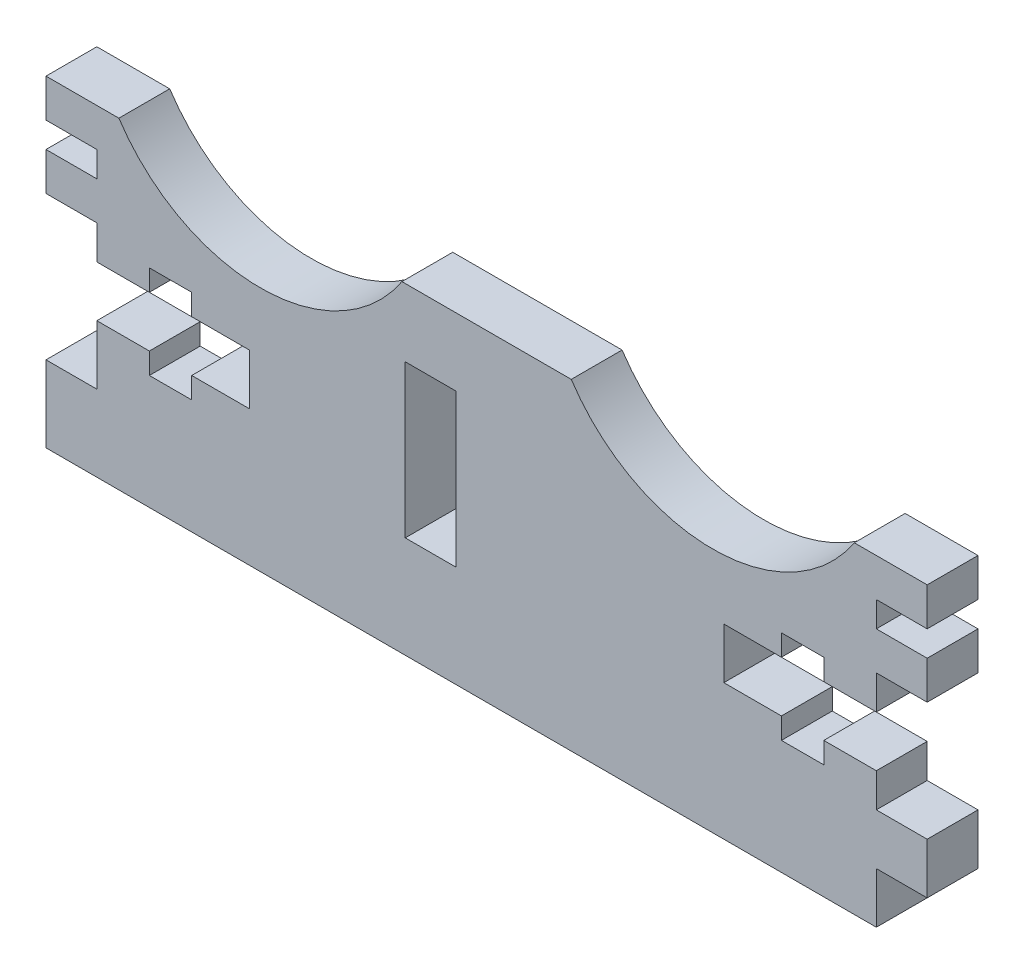
SolidWorks part; units mm, degrees
note: '?' marks a value the reader was unsure of.
material "Acrílico (médio-alto impacto)"
ref_plane "Plano frontal" through (0, 0, 0) normal (0, 0, 1) x (1, 0, 0)
ref_plane "Plano superior" through (0, 0, 0) normal (0, 1, 0) x (1, 0, 0)
ref_plane "Plano direito" through (0, 0, 0) normal (1, 0, 0) x (0, 0, -1)
sketch "Esboço1" plane through (0, 0, 0) normal (0, 0, 1) x (1, 0, 0)
  line L1 (-23, -9.5) -> (23, -9.5)
  line L2 (-23, -9.5) -> (-23, 9.5)
  line L3 (-23, 9.5) -> (23, 9.5)
  line L4 (23, -9.5) -> (23, 9.5)
  line L5 (0, 9.5) -> (0, -9.5) construction
  line L6 (-23, 0) -> (23, 0) construction
  point P0 (0, 0)
  dimension "D1" = 19
  dimension "D2" = 46
sketch "Esboço3" plane through (0, 0, 0) normal (0, 0, 1) x (1, 0, 0)
  line L1 (-23, -9.5) -> (-26, -9.5)
  line L2 (-23, -9.5) -> (-23, -5)
  line L3 (-23, -5) -> (-26, -5)
  line L4 (-26, -9.5) -> (-26, -5)
  dimension "D1" = 4.5
  dimension "D2" = 3
sketch "Esboço5" plane through (0, 0, 0) normal (0, 0, 1) x (1, 0, 0)
  line L0 (-23, -9.5) -> (-23, 9.5) construction
  line L1 (-23, 9.5) -> (-26, 9.5)
  line L2 (-23, 9.5) -> (-23, 7.25)
  line L3 (-23, 7.25) -> (-26, 7.25)
  line L4 (-26, 9.5) -> (-26, 7.25)
  line L5 (-23, 5.75) -> (-26, 5.75)
  line L6 (-23, 5.75) -> (-23, 3.5)
  line L7 (-23, 3.5) -> (-26, 3.5)
  line L8 (-26, 5.75) -> (-26, 3.5)
  line L10 (-26, -9.5) -> (-26, -5) construction
  dimension "D1" = 6
  dimension "D2" = 2.25
sketch "Esboço6" plane through (0, 0, 0) normal (0, 0, 1) x (1, 0, 0)
  line L0 (23, -9.5) -> (23, 9.5) construction
  line L1 (23, -3.5) -> (26, -3.5)
  line L2 (23, -3.5) -> (23, -6.5)
  line L3 (23, -6.5) -> (26, -6.5)
  line L4 (26, -3.5) -> (26, -6.5)
  dimension "D1" = 3
  dimension "D2" = 3
sketch "Esboço7" plane through (0, 0, 0) normal (0, 0, 1) x (1, 0, 0)
  line L0 (0, 9.5) -> (0, -9.5) construction
  line L1 (-23, 9.5) -> (23, 9.5) construction
  line L2 (-21.7, 9.5) -> (-4.9967, 9.5)
  line L3 (4.9967, 9.5) -> (21.7, 9.5)
  line L4 (-23, -9.5) -> (-23, 9.5) construction
  arc A0 (-21.7, 9.5) -> (-4.9967, 9.5) centre (-13.3484, 15) ccw
  arc A1 (4.9967, 9.5) -> (21.7, 9.5) centre (13.3484, 15) ccw
  dimension "D2" = 10
  dimension "D1" = 1.3
  dimension "D3" = 4.5
sketch "Esboço8" plane through (0, 0, 0) normal (0, 0, 1) x (1, 0, 0)
  line L0 (-23, -9.5) -> (23, -9.5) construction
  line L1 (-1.8, 5.5) -> (-4.8, 5.5)
  line L2 (-1.8, 5.5) -> (-1.8, -3.5)
  line L3 (-1.8, -3.5) -> (-4.8, -3.5)
  line L4 (-4.8, 5.5) -> (-4.8, -3.5)
  line L6 (-23, -9.5) -> (-23, 9.5) construction
  dimension "D1" = 6
  dimension "D2" = 9
  dimension "D3" = 3
  dimension "D4" = 18.2
extrude "Ressalto-extrusão1" add sketch "Esboço1" along normal mid plane 3
sketch "Esboço21" plane through (-7.1084, -2.4773, -1.5) normal (0, 0, -1) x (-1, 0, 0)
  line L0 (-30.1084, 2.4773) -> (-21.1084, 2.4773) construction
  line L2 (-30.1084, 11.9773) -> (-30.1084, -7.0227) construction
  line L3 (-30.1084, 0.9773) -> (-21.1084, 0.9773)
  line L4 (-30.1084, 0.9773) -> (-30.1084, 3.9773)
  line L5 (-30.1084, 3.9773) -> (-21.1084, 3.9773)
  line L6 (-21.1084, 0.9773) -> (-21.1084, 3.9773)
  line L7 (-25.6084, 3.9773) -> (-25.6084, 0.9773) construction
  line L8 (-30.1084, 2.4773) -> (-21.1084, 2.4773) construction
  line L9 (-27.0084, 5.2273) -> (-24.5084, 5.2273)
  line L10 (-27.0084, 5.2273) -> (-27.0084, -0.2727)
  line L11 (-27.0084, -0.2727) -> (-24.5084, -0.2727)
  line L12 (-24.5084, 5.2273) -> (-24.5084, -0.2727)
  line L13 (-25.7584, -0.2727) -> (-25.7584, 5.2273) construction
  line L14 (-27.0084, 2.4773) -> (-24.5084, 2.4773) construction
  line L15 (-30.1084, 11.9773) -> (-30.1084, -7.0227) construction
  point P5 (-25.6084, 2.4773)
  point P9 (-25.7584, 2.4773)
  dimension "D1" = 3.1
  dimension "D2" = 5.5
  dimension "D3" = 3
  dimension "D4" = 2.5
  dimension "D6" = 9
  dimension "Posicionar" = 9.5
extrude "Corte-extrusão11" cut sketch "Esboço21" against normal blind 3 contours L5 L6 L3 L4 | L10 L11 L12 L9
other "Porca e parafuso<1>"
mirror "Espelhar4" about plane through (0, 0, 0) normal (1, 0, 0) of "Corte-extrusão11"
ref_axis "Eixo1" through (-23, 0, 0) along (1, 0, 0)?
extrude "Ressalto-extrusão2" add sketch "Esboço3" along normal through all and the other way through all contours L4 L3 L2 L1
extrude "Ressalto-extrusão3" add sketch "Esboço5" along normal through all and the other way through all
mirror "Espelhar3" about plane through (0, 0, 0) normal (1, 0, 0) of "Ressalto-extrusão3"
extrude "Ressalto-extrusão4" add sketch "Esboço6" along normal through all and the other way through all contours L1 L4 L3 L2
extrude "Corte-extrusão2" cut sketch "Esboço7" against normal through all both and the other way through all contours A0 L2
extrude "Corte-extrusão3" cut sketch "Esboço8" against normal through all both and the other way through all contours L2 L3 L4 L1
